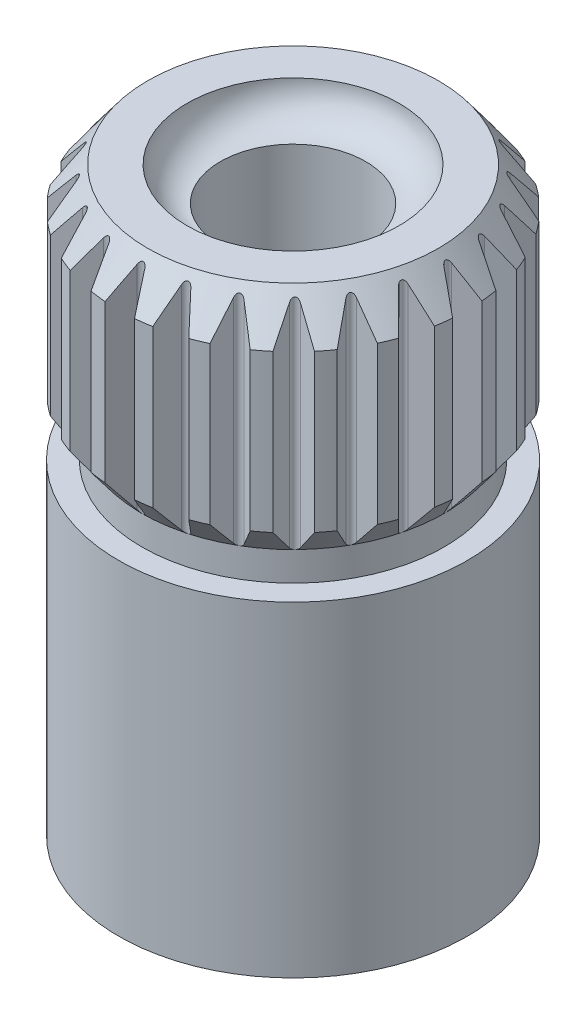
SolidWorks part; units mm, degrees
ref_plane "Ön Düzlem" through (0, 0, 0) normal (0, 0, 1) x (1, 0, 0)
ref_plane "Üst Düzlem" through (0, 0, 0) normal (0, 1, 0) x (1, 0, 0)
ref_plane "Sağ Düzlem" through (0, 0, 0) normal (1, 0, 0) x (0, 0, -1)
sketch "Çizim1" plane through (0, 0, 0) normal (1, 0, 0) x (0, 0, -1)
  line L0 (0, 0) -> (0, 10)
  line L1 (0, 0) -> (-3, 0)
  line L2 (-3, 0) -> (-3, 5.6)
  line L3 (-3, 5.6) -> (-2.6, 5.6)
  line L4 (-2.6, 5.6) -> (-2.6, 6.1)
  line L5 (-3, 6.63) -> (-3, 9.33)
  line L6 (-3, 6.63) -> (-2.6, 6.1)
  line L7 (0, 10) -> (-2.5, 10)
  line L8 (-3, 9.33) -> (-2.5, 10)
  dimension "D1" = 0.53
  dimension "D2" = 0.4
  dimension "D3" = 0.5
  dimension "D4" = 5.6
revolve "Döndür2" add sketch "Çizim1" angle 360 about L0
ref_plane "Düzlem1" through (0, 10, 0) normal (0, 1, 0) x (1, 0, 0)
sketch "Çizim6" plane through (0, 10, 0) normal (0, 1, 0) x (1, 0, 0)
  line L0 (-0.2606, 2.9887) -> (-0.089, 2.6414)
  line L5 (0.043, 2.6407) -> (0.2447, 2.99)
  arc A0 (-0.089, 2.6414) -> (0.043, 2.6407) centre (-0.0229, 2.6741) ccw
  arc A3 (-0.2606, 2.9887) -> (0.2447, 2.99) centre (0, 0) cw
extrude "Kes-Ekstrüzyon2" cut sketch "Çizim6" against normal up to surface (3.37 mm away) up to face at (0, 6.1, -2.6)
pattern_circular "Dairesel Kaplama1" count 25 every 15 about axis through (0, 9.33, 0) along (0, -1, 0) of "Kes-Ekstrüzyon2"
sketch "Çizim7" plane through (0, 10, 0) normal (0, 1, 0) x (1, 0, 0)
  circle A0 centre (0, 0) radius 1.25
  dimension "D1" = 2.5
extrude "Kes-Ekstrüzyon3" cut sketch "Çizim7" against normal blind 9
sketch "Çizim10" plane through (0, 10, 0) normal (0, 1, 0) x (1, 0, 0)
  circle A0 centre (0, 0) radius 1.825
  dimension "D1" = 3.65
extrude "Kes-Ekstrüzyon4" cut sketch "Çizim10" against normal blind 0.58 contours A0
fillet "Radyus3" radius 0.58 1 edges at (0, 9.42, 1.825)
